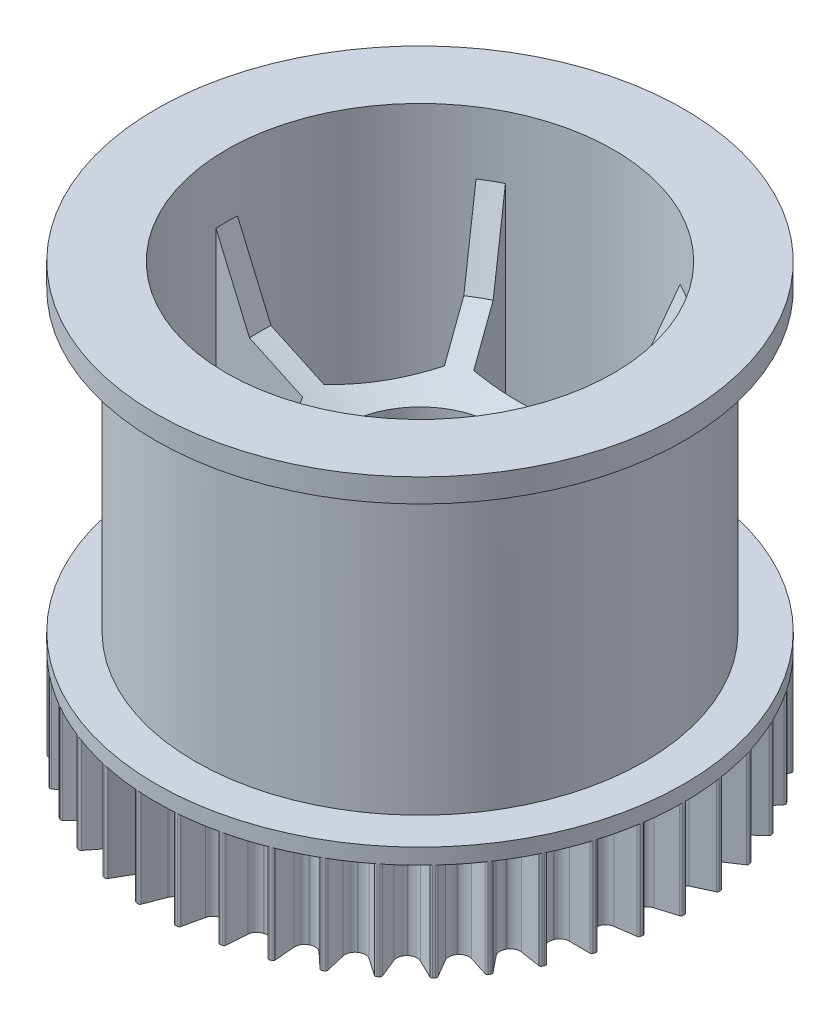
SolidWorks part; units mm, degrees
ref_plane "前视基准面" through (0, 0, 0) normal (0, 0, 1) x (1, 0, 0)
ref_plane "上视基准面" through (0, 0, 0) normal (0, 1, 0) x (1, 0, 0)
ref_plane "右视基准面" through (0, 0, 0) normal (1, 0, 0) x (0, 0, -1)
other "Configuration Table"
sketch "草图1" plane through (0, 0, 0) normal (0, 1, 0) x (1, 0, 0)
  line L0 (0, 0) -> (7.9279, 0) construction
  line L1 (0, 0) -> (0, 4.4256) construction
  line L2 (12.4216, 0.4494) -> (13.4287, 0.1463)
  line L3 (12.4216, -0.4494) -> (13.4287, -0.1463)
  line L4 (12.2159, -2.2957) -> (13.2569, -2.1461)
  line L5 (12.3499, -1.407) -> (13.3005, -1.8568)
  line L6 (11.7373, -4.0908) -> (12.789, -4.098)
  line L7 (12.0023, -3.2319) -> (12.8752, -3.8184)
  line L8 (10.9965, -5.7945) -> (12.0354, -5.9583)
  line L9 (11.3865, -4.9846) -> (12.1623, -5.6947)
  line L10 (10.0101, -7.3687) -> (11.0129, -7.6855)
  line L11 (10.5164, -6.626) -> (11.1777, -7.4438)
  line L12 (8.8, -8.7783) -> (9.7445, -9.2411)
  line L13 (9.4114, -8.1194) -> (9.9434, -9.0266)
  line L14 (7.3934, -9.9918) -> (8.2583, -10.5902)
  line L15 (8.0961, -9.4314) -> (8.487, -10.4078)
  line L16 (5.8216, -10.9822) -> (6.5877, -11.7028)
  line L17 (6.6, -10.5328) -> (6.841, -11.5565)
  line L18 (4.1198, -11.7272) -> (4.7699, -12.5539)
  line L19 (4.9565, -11.3988) -> (5.0422, -12.447)
  line L20 (2.3259, -12.2102) -> (2.8456, -13.1246)
  line L21 (3.2022, -12.0102) -> (3.1308, -13.0595)
  line L22 (0.4801, -12.4205) -> (0.8577, -13.4021)
  line L23 (1.3764, -12.3533) -> (1.1494, -13.3802)
  line L24 (-1.3764, -12.3533) -> (-1.1494, -13.3802)
  line L25 (-0.4801, -12.4205) -> (-0.8577, -13.4021)
  line L26 (-3.2022, -12.0102) -> (-3.1308, -13.0595)
  line L27 (-2.3259, -12.2102) -> (-2.8456, -13.1246)
  line L28 (-4.9565, -11.3988) -> (-5.0422, -12.447)
  line L29 (-4.1198, -11.7272) -> (-4.7699, -12.5539)
  line L30 (-6.6, -10.5328) -> (-6.841, -11.5565)
  line L31 (-5.8216, -10.9822) -> (-6.5877, -11.7028)
  line L32 (-8.0961, -9.4314) -> (-8.487, -10.4078)
  line L33 (-7.3934, -9.9918) -> (-8.2583, -10.5902)
  line L34 (-9.4114, -8.1194) -> (-9.9434, -9.0266)
  line L35 (-8.8, -8.7783) -> (-9.7445, -9.2411)
  line L36 (-10.5164, -6.626) -> (-11.1777, -7.4438)
  line L37 (-10.0101, -7.3687) -> (-11.0129, -7.6855)
  line L38 (-11.3865, -4.9846) -> (-12.1623, -5.6947)
  line L39 (-10.9965, -5.7945) -> (-12.0354, -5.9583)
  line L40 (-12.0023, -3.2319) -> (-12.8752, -3.8184)
  line L41 (-11.7373, -4.0908) -> (-12.789, -4.098)
  line L42 (-12.3499, -1.407) -> (-13.3005, -1.8568)
  line L43 (-12.2159, -2.2957) -> (-13.2569, -2.1461)
  line L44 (-12.4216, 0.4494) -> (-13.4287, 0.1463)
  line L45 (-12.4216, -0.4494) -> (-13.4287, -0.1463)
  line L46 (-12.2159, 2.2957) -> (-13.2569, 2.1461)
  line L47 (-12.3499, 1.407) -> (-13.3005, 1.8568)
  line L48 (-11.7373, 4.0908) -> (-12.789, 4.098)
  line L49 (-12.0023, 3.2319) -> (-12.8752, 3.8184)
  line L50 (-10.9965, 5.7945) -> (-12.0354, 5.9583)
  line L51 (-11.3865, 4.9846) -> (-12.1623, 5.6947)
  line L52 (-10.0101, 7.3687) -> (-11.0129, 7.6855)
  line L53 (-10.5164, 6.626) -> (-11.1777, 7.4438)
  line L54 (-8.8, 8.7783) -> (-9.7445, 9.2411)
  line L55 (-9.4114, 8.1194) -> (-9.9434, 9.0266)
  line L56 (-7.3934, 9.9918) -> (-8.2583, 10.5902)
  line L57 (-8.0961, 9.4314) -> (-8.487, 10.4078)
  line L58 (-5.8216, 10.9822) -> (-6.5877, 11.7028)
  line L59 (-6.6, 10.5328) -> (-6.841, 11.5565)
  line L60 (-4.1198, 11.7272) -> (-4.7699, 12.5539)
  line L61 (-4.9565, 11.3988) -> (-5.0422, 12.447)
  line L62 (-2.3259, 12.2102) -> (-2.8456, 13.1246)
  line L63 (-3.2022, 12.0102) -> (-3.1308, 13.0595)
  line L64 (-0.4801, 12.4205) -> (-0.8577, 13.4021)
  line L65 (-1.3764, 12.3533) -> (-1.1494, 13.3802)
  line L66 (1.3764, 12.3533) -> (1.1494, 13.3802)
  line L67 (0.4801, 12.4205) -> (0.8577, 13.4021)
  line L68 (3.2022, 12.0102) -> (3.1308, 13.0595)
  line L69 (2.3259, 12.2102) -> (2.8456, 13.1246)
  line L70 (4.9565, 11.3988) -> (5.0422, 12.447)
  line L71 (4.1198, 11.7272) -> (4.7699, 12.5539)
  line L72 (6.6, 10.5328) -> (6.841, 11.5565)
  line L73 (5.8216, 10.9822) -> (6.5877, 11.7028)
  line L74 (8.0961, 9.4314) -> (8.487, 10.4078)
  line L75 (7.3934, 9.9918) -> (8.2583, 10.5902)
  line L76 (9.4114, 8.1194) -> (9.9434, 9.0266)
  line L77 (8.8, 8.7783) -> (9.7445, 9.2411)
  line L78 (10.5164, 6.626) -> (11.1777, 7.4438)
  line L79 (10.0101, 7.3687) -> (11.0129, 7.6855)
  line L80 (11.3865, 4.9846) -> (12.1623, 5.6947)
  line L81 (10.9965, 5.7945) -> (12.0354, 5.9583)
  line L82 (12.0023, 3.2319) -> (12.8752, 3.8184)
  line L83 (11.7373, 4.0908) -> (12.789, 4.098)
  line L84 (12.3499, 1.407) -> (13.3005, 1.8568)
  line L85 (12.2159, 2.2957) -> (13.2569, 2.1461)
  line L95 (2.8868, 5) -> (-2.8868, 5) construction
  line L96 (2.8868, 5) -> (5.456, 0.55) construction
  line L97 (0, 0) -> (2.8868, 5) construction
  line L98 (-2.8868, 5) -> (-5.456, 0.55) construction
  line L99 (3.2043, -4.45) -> (5.456, -0.55)
  line L100 (2.2517, -5) -> (-2.2517, -5)
  line L101 (-3.2043, -4.45) -> (-5.456, -0.55)
  line L102 (8.1752, 0) -> (11.2, 0) construction
  line L103 (5.456, 0.55) -> (11.1865, 0.55)
  line L104 (5.456, -0.55) -> (11.1865, -0.55)
  line L105 (3.2043, -4.45) -> (6.0696, -9.4128)
  line L106 (2.2517, -5) -> (5.1169, -9.9628)
  line L107 (-2.2517, -5) -> (-5.1169, -9.9628)
  line L108 (-3.2043, -4.45) -> (-6.0696, -9.4128)
  line L109 (-5.456, -0.55) -> (-11.1865, -0.55)
  line L110 (-5.456, 0.55) -> (-11.1865, 0.55)
  line L111 (-3.2043, 4.45) -> (-6.0696, 9.4128)
  line L112 (-2.2517, 5) -> (-5.1169, 9.9628)
  line L113 (2.2517, 5) -> (5.1169, 9.9628)
  line L114 (3.2043, 4.45) -> (6.0696, 9.4128)
  line L115 (0, 0) -> (12.0337, 1.2648) construction
  line L116 (12.0337, -1.2648) -> (0, 0) construction
  line L117 (-5.456, 0.55) -> (-3.2043, 4.45)
  line L118 (-2.2517, 5) -> (2.2517, 5)
  line L119 (3.2043, 4.45) -> (5.456, 0.55)
  circle A0 centre (0, 0) radius 11.2 construction
  circle A1 centre (0, 0) radius 12.1 construction
  circle A2 centre (0, 0) radius 13.5 construction
  arc A3 (13.4999, 0.0509) -> (13.4999, -0.0509) centre (0, 0) cw
  arc A4 (12.0671, 0.8914) -> (12.0337, 1.2648) centre (0, 0) ccw construction
  arc A5 (13.4287, -0.1463) -> (13.4999, -0.0509) centre (13.3999, -0.0505) ccw
  arc A6 (13.4287, 0.1463) -> (13.4999, 0.0509) centre (13.3999, 0.0505) cw
  arc A7 (12.0671, -0.8914) -> (12.0337, -1.2648) centre (0, 0) cw construction
  arc A8 (12.4216, -0.4494) -> (12.0671, -0.8914) centre (12.5658, -0.9282) ccw
  arc A9 (12.4216, 0.4494) -> (12.0671, 0.8914) centre (12.5658, 0.9282) cw
  arc A10 (12.2159, -2.2957) -> (11.7995, -2.6799) centre (12.2871, -2.7907) ccw
  arc A11 (12.3499, -1.407) -> (12.0652, -0.9171) centre (12.5638, -0.955) cw
  arc A12 (13.3005, -1.8568) -> (13.3567, -1.9617) centre (13.2578, -1.9472) cw
  arc A13 (13.3567, -1.9617) -> (13.3415, -2.0624) centre (0, 0) cw
  arc A14 (13.2569, -2.1461) -> (13.3415, -2.0624) centre (13.2427, -2.0471) ccw
  arc A15 (11.7373, -4.0908) -> (11.2683, -4.4086) centre (11.7339, -4.5908) ccw
  arc A16 (12.0023, -3.2319) -> (11.7937, -2.7051) centre (12.2811, -2.8169) cw
  arc A17 (12.8752, -3.8184) -> (12.9151, -3.9305) centre (12.8195, -3.9014) cw
  arc A18 (12.9151, -3.9305) -> (12.8851, -4.0278) centre (0, 0) cw
  arc A19 (12.789, -4.098) -> (12.8851, -4.0278) centre (12.7897, -3.998) ccw
  arc A20 (10.9965, -5.7945) -> (10.4854, -6.0388) centre (10.9186, -6.2884) ccw
  arc A21 (11.3865, -4.9846) -> (11.2589, -4.4326) centre (11.7241, -4.6158) cw
  arc A22 (12.1623, -5.6947) -> (12.1851, -5.8115) centre (12.0948, -5.7685) cw
  arc A23 (12.1851, -5.8115) -> (12.1409, -5.9032) centre (0, 0) cw
  arc A24 (12.0354, -5.9583) -> (12.1409, -5.9032) centre (12.051, -5.8595) ccw
  arc A25 (10.0101, -7.3687) -> (9.4682, -7.5341) centre (9.8595, -7.8455) ccw
  arc A26 (10.5164, -6.626) -> (10.4724, -6.0612) centre (10.9052, -6.3116) cw
  arc A27 (11.1777, -7.4438) -> (11.1828, -7.5627) centre (11.1, -7.5067) cw
  arc A28 (11.1828, -7.5627) -> (11.1255, -7.6468) centre (0, 0) cw
  arc A29 (11.0129, -7.6855) -> (11.1255, -7.6468) centre (11.0431, -7.5902) ccw
  arc A30 (8.8, -8.7783) -> (8.2395, -8.8611) centre (8.58, -9.2273) ccw
  arc A31 (9.4114, -8.1194) -> (9.4521, -7.5543) centre (9.8427, -7.8665) cw
  arc A32 (9.9434, -9.0266) -> (9.9308, -9.145) centre (9.8572, -9.0772) cw
  arc A33 (9.9308, -9.145) -> (9.8615, -9.2196) centre (0, 0) cw
  arc A34 (9.7445, -9.2411) -> (9.8615, -9.2196) centre (9.7885, -9.1513) ccw
  arc A35 (7.3934, -9.9918) -> (6.8268, -9.9902) centre (7.1089, -10.403) ccw
  arc A36 (8.0961, -9.4314) -> (8.2206, -8.8787) centre (8.5603, -9.2456) cw
  arc A37 (8.487, -10.4078) -> (8.4568, -10.5229) centre (8.3942, -10.445) cw
  arc A38 (8.4568, -10.5229) -> (8.3773, -10.5864) centre (0, 0) cw
  arc A39 (8.2583, -10.5902) -> (8.3773, -10.5864) centre (8.3152, -10.508) ccw
  arc A40 (5.8216, -10.9822) -> (5.2616, -10.8961) centre (5.479, -11.3464) ccw
  arc A41 (6.6, -10.5328) -> (6.8055, -10.0048) centre (7.0867, -10.4182) cw
  arc A42 (6.841, -11.5565) -> (6.794, -11.6658) centre (6.7437, -11.5794) cw
  arc A43 (6.794, -11.6658) -> (6.7059, -11.7167) centre (0, 0) cw
  arc A44 (6.5877, -11.7028) -> (6.7059, -11.7167) centre (6.6562, -11.6299) ccw
  arc A45 (4.1198, -11.7272) -> (3.5789, -11.5586) centre (3.7268, -12.0362) ccw
  arc A46 (4.9565, -11.3988) -> (5.2384, -10.9073) centre (5.4548, -11.358) cw
  arc A47 (5.0422, -12.447) -> (4.9795, -12.5481) centre (4.9426, -12.4552) cw
  arc A48 (4.9795, -12.5481) -> (4.8847, -12.5853) centre (0, 0) cw
  arc A49 (4.7699, -12.5539) -> (4.8847, -12.5853) centre (4.8485, -12.4921) ccw
  arc A50 (2.3259, -12.2102) -> (1.8162, -11.9629) centre (1.8912, -12.4573) ccw
  arc A51 (3.2022, -12.0102) -> (3.5542, -11.5662) centre (3.7011, -12.0442) cw
  arc A52 (3.1308, -13.0595) -> (3.0536, -13.1501) centre (3.031, -13.0527) cw
  arc A53 (3.0536, -13.1501) -> (2.9544, -13.1728) centre (0, 0) cw
  arc A54 (2.8456, -13.1246) -> (2.9544, -13.1728) centre (2.9325, -13.0752) ccw
  arc A55 (0.4801, -12.4205) -> (0.0129, -12.1) centre (0.0134, -12.6) ccw
  arc A56 (1.3764, -12.3533) -> (1.7906, -11.9668) centre (1.8646, -12.4613) cw
  arc A57 (1.1494, -13.3802) -> (1.0596, -13.4584) centre (1.0518, -13.3587) cw
  arc A58 (1.0596, -13.4584) -> (0.9581, -13.466) centre (0, 0) cw
  arc A59 (0.8577, -13.4021) -> (0.9581, -13.466) centre (0.951, -13.3662) ccw
  arc A60 (-1.3764, -12.3533) -> (-1.7906, -11.9668) centre (-1.8646, -12.4613) ccw
  arc A61 (-0.4801, -12.4205) -> (-0.0129, -12.1) centre (-0.0134, -12.6) cw
  arc A62 (-0.8577, -13.4021) -> (-0.9581, -13.466) centre (-0.951, -13.3662) cw
  arc A63 (-0.9581, -13.466) -> (-1.0596, -13.4584) centre (0, 0) cw
  arc A64 (-1.1494, -13.3802) -> (-1.0596, -13.4584) centre (-1.0518, -13.3587) ccw
  arc A65 (-3.2022, -12.0102) -> (-3.5542, -11.5662) centre (-3.7011, -12.0442) ccw
  arc A66 (-2.3259, -12.2102) -> (-1.8162, -11.9629) centre (-1.8912, -12.4573) cw
  arc A67 (-2.8456, -13.1246) -> (-2.9544, -13.1728) centre (-2.9325, -13.0752) cw
  arc A68 (-2.9544, -13.1728) -> (-3.0536, -13.1501) centre (0, 0) cw
  arc A69 (-3.1308, -13.0595) -> (-3.0536, -13.1501) centre (-3.031, -13.0527) ccw
  arc A70 (-4.9565, -11.3988) -> (-5.2384, -10.9073) centre (-5.4548, -11.358) ccw
  arc A71 (-4.1198, -11.7272) -> (-3.5789, -11.5586) centre (-3.7268, -12.0362) cw
  arc A72 (-4.7699, -12.5539) -> (-4.8847, -12.5853) centre (-4.8485, -12.4921) cw
  arc A73 (-4.8847, -12.5853) -> (-4.9795, -12.5481) centre (0, 0) cw
  arc A74 (-5.0422, -12.447) -> (-4.9795, -12.5481) centre (-4.9426, -12.4552) ccw
  arc A75 (-6.6, -10.5328) -> (-6.8055, -10.0048) centre (-7.0867, -10.4182) ccw
  arc A76 (-5.8216, -10.9822) -> (-5.2616, -10.8961) centre (-5.479, -11.3464) cw
  arc A77 (-6.5877, -11.7028) -> (-6.7059, -11.7167) centre (-6.6562, -11.6299) cw
  arc A78 (-6.7059, -11.7167) -> (-6.794, -11.6658) centre (0, 0) cw
  arc A79 (-6.841, -11.5565) -> (-6.794, -11.6658) centre (-6.7437, -11.5794) ccw
  arc A80 (-8.0961, -9.4314) -> (-8.2206, -8.8787) centre (-8.5603, -9.2456) ccw
  arc A81 (-7.3934, -9.9918) -> (-6.8268, -9.9902) centre (-7.1089, -10.403) cw
  arc A82 (-8.2583, -10.5902) -> (-8.3773, -10.5864) centre (-8.3152, -10.508) cw
  arc A83 (-8.3773, -10.5864) -> (-8.4568, -10.5229) centre (0, 0) cw
  arc A84 (-8.487, -10.4078) -> (-8.4568, -10.5229) centre (-8.3942, -10.445) ccw
  arc A85 (-9.4114, -8.1194) -> (-9.4521, -7.5543) centre (-9.8427, -7.8665) ccw
  arc A86 (-8.8, -8.7783) -> (-8.2395, -8.8611) centre (-8.58, -9.2273) cw
  arc A87 (-9.7445, -9.2411) -> (-9.8615, -9.2196) centre (-9.7885, -9.1513) cw
  arc A88 (-9.8615, -9.2196) -> (-9.9308, -9.145) centre (0, 0) cw
  arc A89 (-9.9434, -9.0266) -> (-9.9308, -9.145) centre (-9.8572, -9.0772) ccw
  arc A90 (-10.5164, -6.626) -> (-10.4724, -6.0612) centre (-10.9052, -6.3116) ccw
  arc A91 (-10.0101, -7.3687) -> (-9.4682, -7.5341) centre (-9.8595, -7.8455) cw
  arc A92 (-11.0129, -7.6855) -> (-11.1255, -7.6468) centre (-11.0431, -7.5902) cw
  arc A93 (-11.1255, -7.6468) -> (-11.1828, -7.5627) centre (0, 0) cw
  arc A94 (-11.1777, -7.4438) -> (-11.1828, -7.5627) centre (-11.1, -7.5067) ccw
  arc A95 (-11.3865, -4.9846) -> (-11.2589, -4.4326) centre (-11.7241, -4.6158) ccw
  arc A96 (-10.9965, -5.7945) -> (-10.4854, -6.0388) centre (-10.9186, -6.2884) cw
  arc A97 (-12.0354, -5.9583) -> (-12.1409, -5.9032) centre (-12.051, -5.8595) cw
  arc A98 (-12.1409, -5.9032) -> (-12.1851, -5.8115) centre (0, 0) cw
  arc A99 (-12.1623, -5.6947) -> (-12.1851, -5.8115) centre (-12.0948, -5.7685) ccw
  arc A100 (-12.0023, -3.2319) -> (-11.7937, -2.7051) centre (-12.2811, -2.8169) ccw
  arc A101 (-11.7373, -4.0908) -> (-11.2683, -4.4086) centre (-11.7339, -4.5908) cw
  arc A102 (-12.789, -4.098) -> (-12.8851, -4.0278) centre (-12.7897, -3.998) cw
  arc A103 (-12.8851, -4.0278) -> (-12.9151, -3.9305) centre (0, 0) cw
  arc A104 (-12.8752, -3.8184) -> (-12.9151, -3.9305) centre (-12.8195, -3.9014) ccw
  arc A105 (-12.3499, -1.407) -> (-12.0652, -0.9171) centre (-12.5638, -0.955) ccw
  arc A106 (-12.2159, -2.2957) -> (-11.7995, -2.6799) centre (-12.2871, -2.7907) cw
  arc A107 (-13.2569, -2.1461) -> (-13.3415, -2.0624) centre (-13.2427, -2.0471) cw
  arc A108 (-13.3415, -2.0624) -> (-13.3567, -1.9617) centre (0, 0) cw
  arc A109 (-13.3005, -1.8568) -> (-13.3567, -1.9617) centre (-13.2578, -1.9472) ccw
  arc A110 (-12.4216, 0.4494) -> (-12.0671, 0.8914) centre (-12.5658, 0.9282) ccw
  arc A111 (-12.4216, -0.4494) -> (-12.0671, -0.8914) centre (-12.5658, -0.9282) cw
  arc A112 (-13.4287, -0.1463) -> (-13.4999, -0.0509) centre (-13.3999, -0.0505) cw
  arc A113 (-13.4999, -0.0509) -> (-13.4999, 0.0509) centre (0, 0) cw
  arc A114 (-13.4287, 0.1463) -> (-13.4999, 0.0509) centre (-13.3999, 0.0505) ccw
  arc A115 (-12.2159, 2.2957) -> (-11.7995, 2.6799) centre (-12.2871, 2.7907) ccw
  arc A116 (-12.3499, 1.407) -> (-12.0652, 0.9171) centre (-12.5638, 0.955) cw
  arc A117 (-13.3005, 1.8568) -> (-13.3567, 1.9617) centre (-13.2578, 1.9472) cw
  arc A118 (-13.3567, 1.9617) -> (-13.3415, 2.0624) centre (0, 0) cw
  arc A119 (-13.2569, 2.1461) -> (-13.3415, 2.0624) centre (-13.2427, 2.0471) ccw
  arc A120 (-11.7373, 4.0908) -> (-11.2683, 4.4086) centre (-11.7339, 4.5908) ccw
  arc A121 (-12.0023, 3.2319) -> (-11.7937, 2.7051) centre (-12.2811, 2.8169) cw
  arc A122 (-12.8752, 3.8184) -> (-12.9151, 3.9305) centre (-12.8195, 3.9014) cw
  arc A123 (-12.9151, 3.9305) -> (-12.8851, 4.0278) centre (0, 0) cw
  arc A124 (-12.789, 4.098) -> (-12.8851, 4.0278) centre (-12.7897, 3.998) ccw
  arc A125 (-10.9965, 5.7945) -> (-10.4854, 6.0388) centre (-10.9186, 6.2884) ccw
  arc A126 (-11.3865, 4.9846) -> (-11.2589, 4.4326) centre (-11.7241, 4.6158) cw
  arc A127 (-12.1623, 5.6947) -> (-12.1851, 5.8115) centre (-12.0948, 5.7685) cw
  arc A128 (-12.1851, 5.8115) -> (-12.1409, 5.9032) centre (0, 0) cw
  arc A129 (-12.0354, 5.9583) -> (-12.1409, 5.9032) centre (-12.051, 5.8595) ccw
  arc A130 (-10.0101, 7.3687) -> (-9.4682, 7.5341) centre (-9.8595, 7.8455) ccw
  arc A131 (-10.5164, 6.626) -> (-10.4724, 6.0612) centre (-10.9052, 6.3116) cw
  arc A132 (-11.1777, 7.4438) -> (-11.1828, 7.5627) centre (-11.1, 7.5067) cw
  arc A133 (-11.1828, 7.5627) -> (-11.1255, 7.6468) centre (0, 0) cw
  arc A134 (-11.0129, 7.6855) -> (-11.1255, 7.6468) centre (-11.0431, 7.5902) ccw
  arc A135 (-8.8, 8.7783) -> (-8.2395, 8.8611) centre (-8.58, 9.2273) ccw
  arc A136 (-9.4114, 8.1194) -> (-9.4521, 7.5543) centre (-9.8427, 7.8665) cw
  arc A137 (-9.9434, 9.0266) -> (-9.9308, 9.145) centre (-9.8572, 9.0772) cw
  arc A138 (-9.9308, 9.145) -> (-9.8615, 9.2196) centre (0, 0) cw
  arc A139 (-9.7445, 9.2411) -> (-9.8615, 9.2196) centre (-9.7885, 9.1513) ccw
  arc A140 (-7.3934, 9.9918) -> (-6.8268, 9.9902) centre (-7.1089, 10.403) ccw
  arc A141 (-8.0961, 9.4314) -> (-8.2206, 8.8787) centre (-8.5603, 9.2456) cw
  arc A142 (-8.487, 10.4078) -> (-8.4568, 10.5229) centre (-8.3942, 10.445) cw
  arc A143 (-8.4568, 10.5229) -> (-8.3773, 10.5864) centre (0, 0) cw
  arc A144 (-8.2583, 10.5902) -> (-8.3773, 10.5864) centre (-8.3152, 10.508) ccw
  arc A145 (-5.8216, 10.9822) -> (-5.2616, 10.8961) centre (-5.479, 11.3464) ccw
  arc A146 (-6.6, 10.5328) -> (-6.8055, 10.0048) centre (-7.0867, 10.4182) cw
  arc A147 (-6.841, 11.5565) -> (-6.794, 11.6658) centre (-6.7437, 11.5794) cw
  arc A148 (-6.794, 11.6658) -> (-6.7059, 11.7167) centre (0, 0) cw
  arc A149 (-6.5877, 11.7028) -> (-6.7059, 11.7167) centre (-6.6562, 11.6299) ccw
  arc A150 (-4.1198, 11.7272) -> (-3.5789, 11.5586) centre (-3.7268, 12.0362) ccw
  arc A151 (-4.9565, 11.3988) -> (-5.2384, 10.9073) centre (-5.4548, 11.358) cw
  arc A152 (-5.0422, 12.447) -> (-4.9795, 12.5481) centre (-4.9426, 12.4552) cw
  arc A153 (-4.9795, 12.5481) -> (-4.8847, 12.5853) centre (0, 0) cw
  arc A154 (-4.7699, 12.5539) -> (-4.8847, 12.5853) centre (-4.8485, 12.4921) ccw
  arc A155 (-2.3259, 12.2102) -> (-1.8162, 11.9629) centre (-1.8912, 12.4573) ccw
  arc A156 (-3.2022, 12.0102) -> (-3.5542, 11.5662) centre (-3.7011, 12.0442) cw
  arc A157 (-3.1308, 13.0595) -> (-3.0536, 13.1501) centre (-3.031, 13.0527) cw
  arc A158 (-3.0536, 13.1501) -> (-2.9544, 13.1728) centre (0, 0) cw
  arc A159 (-2.8456, 13.1246) -> (-2.9544, 13.1728) centre (-2.9325, 13.0752) ccw
  arc A160 (-0.4801, 12.4205) -> (-0.0129, 12.1) centre (-0.0134, 12.6) ccw
  arc A161 (-1.3764, 12.3533) -> (-1.7906, 11.9668) centre (-1.8646, 12.4613) cw
  arc A162 (-1.1494, 13.3802) -> (-1.0596, 13.4584) centre (-1.0518, 13.3587) cw
  arc A163 (-1.0596, 13.4584) -> (-0.9581, 13.466) centre (0, 0) cw
  arc A164 (-0.8577, 13.4021) -> (-0.9581, 13.466) centre (-0.951, 13.3662) ccw
  arc A165 (1.3764, 12.3533) -> (1.7906, 11.9668) centre (1.8646, 12.4613) ccw
  arc A166 (0.4801, 12.4205) -> (0.0129, 12.1) centre (0.0134, 12.6) cw
  arc A167 (0.8577, 13.4021) -> (0.9581, 13.466) centre (0.951, 13.3662) cw
  arc A168 (0.9581, 13.466) -> (1.0596, 13.4584) centre (0, 0) cw
  arc A169 (1.1494, 13.3802) -> (1.0596, 13.4584) centre (1.0518, 13.3587) ccw
  arc A170 (3.2022, 12.0102) -> (3.5542, 11.5662) centre (3.7011, 12.0442) ccw
  arc A171 (2.3259, 12.2102) -> (1.8162, 11.9629) centre (1.8912, 12.4573) cw
  arc A172 (2.8456, 13.1246) -> (2.9544, 13.1728) centre (2.9325, 13.0752) cw
  arc A173 (2.9544, 13.1728) -> (3.0536, 13.1501) centre (0, 0) cw
  arc A174 (3.1308, 13.0595) -> (3.0536, 13.1501) centre (3.031, 13.0527) ccw
  arc A175 (4.9565, 11.3988) -> (5.2384, 10.9073) centre (5.4548, 11.358) ccw
  arc A176 (4.1198, 11.7272) -> (3.5789, 11.5586) centre (3.7268, 12.0362) cw
  arc A177 (4.7699, 12.5539) -> (4.8847, 12.5853) centre (4.8485, 12.4921) cw
  arc A178 (4.8847, 12.5853) -> (4.9795, 12.5481) centre (0, 0) cw
  arc A179 (5.0422, 12.447) -> (4.9795, 12.5481) centre (4.9426, 12.4552) ccw
  arc A180 (6.6, 10.5328) -> (6.8055, 10.0048) centre (7.0867, 10.4182) ccw
  arc A181 (5.8216, 10.9822) -> (5.2616, 10.8961) centre (5.479, 11.3464) cw
  arc A182 (6.5877, 11.7028) -> (6.7059, 11.7167) centre (6.6562, 11.6299) cw
  arc A183 (6.7059, 11.7167) -> (6.794, 11.6658) centre (0, 0) cw
  arc A184 (6.841, 11.5565) -> (6.794, 11.6658) centre (6.7437, 11.5794) ccw
  arc A185 (8.0961, 9.4314) -> (8.2206, 8.8787) centre (8.5603, 9.2456) ccw
  arc A186 (7.3934, 9.9918) -> (6.8268, 9.9902) centre (7.1089, 10.403) cw
  arc A187 (8.2583, 10.5902) -> (8.3773, 10.5864) centre (8.3152, 10.508) cw
  arc A188 (8.3773, 10.5864) -> (8.4568, 10.5229) centre (0, 0) cw
  arc A189 (8.487, 10.4078) -> (8.4568, 10.5229) centre (8.3942, 10.445) ccw
  arc A190 (9.4114, 8.1194) -> (9.4521, 7.5543) centre (9.8427, 7.8665) ccw
  arc A191 (8.8, 8.7783) -> (8.2395, 8.8611) centre (8.58, 9.2273) cw
  arc A192 (9.7445, 9.2411) -> (9.8615, 9.2196) centre (9.7885, 9.1513) cw
  arc A193 (9.8615, 9.2196) -> (9.9308, 9.145) centre (0, 0) cw
  arc A194 (9.9434, 9.0266) -> (9.9308, 9.145) centre (9.8572, 9.0772) ccw
  arc A195 (10.5164, 6.626) -> (10.4724, 6.0612) centre (10.9052, 6.3116) ccw
  arc A196 (10.0101, 7.3687) -> (9.4682, 7.5341) centre (9.8595, 7.8455) cw
  arc A197 (11.0129, 7.6855) -> (11.1255, 7.6468) centre (11.0431, 7.5902) cw
  arc A198 (11.1255, 7.6468) -> (11.1828, 7.5627) centre (0, 0) cw
  arc A199 (11.1777, 7.4438) -> (11.1828, 7.5627) centre (11.1, 7.5067) ccw
  arc A200 (11.3865, 4.9846) -> (11.2589, 4.4326) centre (11.7241, 4.6158) ccw
  arc A201 (10.9965, 5.7945) -> (10.4854, 6.0388) centre (10.9186, 6.2884) cw
  arc A202 (12.0354, 5.9583) -> (12.1409, 5.9032) centre (12.051, 5.8595) cw
  arc A203 (12.1409, 5.9032) -> (12.1851, 5.8115) centre (0, 0) cw
  arc A204 (12.1623, 5.6947) -> (12.1851, 5.8115) centre (12.0948, 5.7685) ccw
  arc A205 (12.0023, 3.2319) -> (11.7937, 2.7051) centre (12.2811, 2.8169) ccw
  arc A206 (11.7373, 4.0908) -> (11.2683, 4.4086) centre (11.7339, 4.5908) cw
  arc A207 (12.789, 4.098) -> (12.8851, 4.0278) centre (12.7897, 3.998) cw
  arc A208 (12.8851, 4.0278) -> (12.9151, 3.9305) centre (0, 0) cw
  arc A209 (12.8752, 3.8184) -> (12.9151, 3.9305) centre (12.8195, 3.9014) ccw
  arc A210 (12.3499, 1.407) -> (12.0652, 0.9171) centre (12.5638, 0.955) ccw
  arc A211 (12.2159, 2.2957) -> (11.7995, 2.6799) centre (12.2871, 2.7907) cw
  arc A212 (13.2569, 2.1461) -> (13.3415, 2.0624) centre (13.2427, 2.0471) cw
  arc A213 (13.3415, 2.0624) -> (13.3567, 1.9617) centre (0, 0) cw
  arc A214 (13.3005, 1.8568) -> (13.3567, 1.9617) centre (13.2578, 1.9472) ccw
  circle A216 centre (0, 0) radius 3.9
  arc A217 (11.1865, 0.55) -> (6.0696, 9.4128) centre (0, 0) ccw
  arc A218 (5.1169, 9.9628) -> (-5.1169, 9.9628) centre (0, 0) ccw
  arc A219 (-6.0696, 9.4128) -> (-11.1865, 0.55) centre (0, 0) ccw
  arc A220 (-11.1865, -0.55) -> (-6.0696, -9.4128) centre (0, 0) ccw
  arc A221 (-5.1169, -9.9628) -> (5.1169, -9.9628) centre (0, 0) ccw
  arc A222 (6.0696, -9.4128) -> (11.1865, -0.55) centre (0, 0) ccw
  arc A223 (12.0652, 0.9171) -> (12.0671, 0.8914) centre (0, 0) cw
  arc A224 (12.0671, -0.8914) -> (12.0652, -0.9171) centre (0, 0) cw
  arc A225 (11.7995, -2.6799) -> (11.7937, -2.7051) centre (0, 0) cw
  arc A226 (11.2683, -4.4086) -> (11.2589, -4.4326) centre (0, 0) cw
  arc A227 (10.4854, -6.0388) -> (10.4724, -6.0612) centre (0, 0) cw
  arc A228 (9.4682, -7.5341) -> (9.4521, -7.5543) centre (0, 0) cw
  arc A229 (8.2395, -8.8611) -> (8.2206, -8.8787) centre (0, 0) cw
  arc A230 (6.8268, -9.9902) -> (6.8055, -10.0048) centre (0, 0) cw
  arc A231 (5.2616, -10.8961) -> (5.2384, -10.9073) centre (0, 0) cw
  arc A232 (3.5789, -11.5586) -> (3.5542, -11.5662) centre (0, 0) cw
  arc A233 (1.8162, -11.9629) -> (1.7906, -11.9668) centre (0, 0) cw
  arc A234 (0.0129, -12.1) -> (-0.0129, -12.1) centre (0, 0) cw
  arc A235 (-1.7906, -11.9668) -> (-1.8162, -11.9629) centre (0, 0) cw
  arc A236 (-3.5542, -11.5662) -> (-3.5789, -11.5586) centre (0, 0) cw
  arc A237 (-5.2384, -10.9073) -> (-5.2616, -10.8961) centre (0, 0) cw
  arc A238 (-6.8055, -10.0048) -> (-6.8268, -9.9902) centre (0, 0) cw
  arc A239 (-8.2206, -8.8787) -> (-8.2395, -8.8611) centre (0, 0) cw
  arc A240 (-9.4521, -7.5543) -> (-9.4682, -7.5341) centre (0, 0) cw
  arc A241 (-10.4724, -6.0612) -> (-10.4854, -6.0388) centre (0, 0) cw
  arc A242 (-11.2589, -4.4326) -> (-11.2683, -4.4086) centre (0, 0) cw
  arc A243 (-11.7937, -2.7051) -> (-11.7995, -2.6799) centre (0, 0) cw
  arc A244 (-12.0652, -0.9171) -> (-12.0671, -0.8914) centre (0, 0) cw
  arc A245 (-12.0671, 0.8914) -> (-12.0652, 0.9171) centre (0, 0) cw
  arc A246 (-11.7995, 2.6799) -> (-11.7937, 2.7051) centre (0, 0) cw
  arc A247 (-11.2683, 4.4086) -> (-11.2589, 4.4326) centre (0, 0) cw
  arc A248 (-10.4854, 6.0388) -> (-10.4724, 6.0612) centre (0, 0) cw
  arc A249 (-9.4682, 7.5341) -> (-9.4521, 7.5543) centre (0, 0) cw
  arc A250 (-8.2395, 8.8611) -> (-8.2206, 8.8787) centre (0, 0) cw
  arc A251 (-6.8268, 9.9902) -> (-6.8055, 10.0048) centre (0, 0) cw
  arc A252 (-5.2616, 10.8961) -> (-5.2384, 10.9073) centre (0, 0) cw
  arc A253 (-3.5789, 11.5586) -> (-3.5542, 11.5662) centre (0, 0) cw
  arc A254 (-1.8162, 11.9629) -> (-1.7906, 11.9668) centre (0, 0) cw
  arc A255 (-0.0129, 12.1) -> (0.0129, 12.1) centre (0, 0) cw
  arc A256 (1.7906, 11.9668) -> (1.8162, 11.9629) centre (0, 0) cw
  arc A257 (3.5542, 11.5662) -> (3.5789, 11.5586) centre (0, 0) cw
  arc A258 (5.2384, 10.9073) -> (5.2616, 10.8961) centre (0, 0) cw
  arc A259 (6.8055, 10.0048) -> (6.8268, 9.9902) centre (0, 0) cw
  arc A260 (8.2206, 8.8787) -> (8.2395, 8.8611) centre (0, 0) cw
  arc A261 (9.4521, 7.5543) -> (9.4682, 7.5341) centre (0, 0) cw
  arc A262 (10.4724, 6.0612) -> (10.4854, 6.0388) centre (0, 0) cw
  arc A263 (11.2589, 4.4326) -> (11.2683, 4.4086) centre (0, 0) cw
  arc A264 (11.7937, 2.7051) -> (11.7995, 2.6799) centre (0, 0) cw
  point P17 (13.4994, -0.125)
  point P20 (13.4994, 0.125)
  point P23 (12.0875, -0.55)
  point P26 (12.0875, 0.55)
  point P524 (0, 5)
  dimension "D1" = 22.4
  dimension "D2" = 24.2
  dimension "D3" = 27
  dimension "D6" = 0.1
  dimension "D7" = 0.5
  dimension "D9" = 120
  dimension "D12" = 7.8
  dimension "D4" = 1.1
  dimension "D5" = 0.25
  dimension "D10" = 5
  dimension "D11" = 30
  dimension "D14" = 1.1
  dimension "D16" = 6
  dimension "D17" = 6
  dimension "D8" = 42
  dimension "D13" = 6
  dimension "D15" = 42
extrude "凸台-拉伸1" add sketch "草图1" along normal blind 5
sketch "草图2" plane through (0, 5, 0) normal (0, 1, 0) x (1, 0, 0)
  circle A0 centre (0, 0) radius 13.5
  arc A1 (13.3415, -2.0624) -> (13.3567, -1.9617) centre (0, 0) ccw construction
  circle A2 centre (0, 0) radius 11.2
  arc A3 (6.0696, -9.4128) -> (11.1865, -0.55) centre (0, 0) ccw construction
extrude "凸台-拉伸2" add sketch "草图2" along normal blind 0.8
extrude "拉伸-薄壁2" add sketch "草图2<2>" along normal blind 16 thin contours A2 thin type mid plane wall 0.6
sketch "草图2<2>" plane through (0, 5, 0) normal (0, 1, 0) x (1, 0, 0) same geometry as "草图2"
sketch "草图5" plane through (0, 21, 0) normal (0, 1, 0) x (1, 0, 0)
  circle A0 centre (0, 0) radius 13.5
  circle A1 centre (0, 0) radius 13.5 construction
  circle A2 centre (0, 0) radius 10.9
  circle A3 centre (0, 0) radius 10.9 construction
extrude "凸台-拉伸3" add sketch "草图5" along normal blind 1.2
sketch "草图6" plane through (0, 5, 0) normal (0, 1, 0) x (1, 0, 0)
  line L18 (-4.9667, -9.7027) -> (-2.2517, -5)
  line L19 (-2.2517, -5) -> (2.2517, -5)
  line L20 (2.2517, -5) -> (4.9667, -9.7027)
  line L21 (5.9194, -9.1527) -> (3.2043, -4.45)
  line L22 (3.2043, -4.45) -> (5.456, -0.55)
  line L23 (5.456, -0.55) -> (10.8861, -0.55)
  line L24 (10.8861, 0.55) -> (5.456, 0.55)
  line L25 (5.456, 0.55) -> (3.2043, 4.45)
  line L26 (3.2043, 4.45) -> (5.9194, 9.1527)
  line L27 (4.9667, 9.7027) -> (2.2517, 5)
  line L28 (2.2517, 5) -> (-2.2517, 5)
  line L29 (-2.2517, 5) -> (-4.9667, 9.7027)
  line L30 (-5.9194, 9.1527) -> (-3.2043, 4.45)
  line L31 (-3.2043, 4.45) -> (-5.456, 0.55)
  line L32 (-5.456, 0.55) -> (-10.8861, 0.55)
  line L33 (-10.8861, -0.55) -> (-5.456, -0.55)
  line L34 (-5.456, -0.55) -> (-3.2043, -4.45)
  line L35 (-3.2043, -4.45) -> (-5.9194, -9.1527)
  line L36 (-4.9667, -9.7027) -> (-2.2517, -5)
  line L37 (-2.2517, -5) -> (2.2517, -5)
  line L38 (2.2517, -5) -> (4.9667, -9.7027)
  line L39 (5.9194, -9.1527) -> (3.2043, -4.45)
  line L40 (3.2043, -4.45) -> (5.456, -0.55)
  line L41 (5.456, -0.55) -> (10.8861, -0.55)
  line L42 (10.8861, 0.55) -> (5.456, 0.55)
  line L43 (5.456, 0.55) -> (3.2043, 4.45)
  line L44 (3.2043, 4.45) -> (5.9194, 9.1527)
  line L45 (4.9667, 9.7027) -> (2.2517, 5)
  line L46 (2.2517, 5) -> (-2.2517, 5)
  line L47 (-2.2517, 5) -> (-4.9667, 9.7027)
  line L48 (-5.9194, 9.1527) -> (-3.2043, 4.45)
  line L49 (-3.2043, 4.45) -> (-5.456, 0.55)
  line L50 (-5.456, 0.55) -> (-10.8861, 0.55)
  line L51 (-10.8861, -0.55) -> (-5.456, -0.55)
  line L52 (-5.456, -0.55) -> (-3.2043, -4.45)
  line L53 (-3.2043, -4.45) -> (-5.9194, -9.1527)
  circle A0 centre (0, 0) radius 3.9
  circle A1 centre (0, 0) radius 3.9 construction
  arc A6 (-5.9194, -9.1527) -> (-4.9667, -9.7027) centre (0, 0) ccw
  arc A7 (4.9667, -9.7027) -> (5.9194, -9.1527) centre (0, 0) ccw
  arc A8 (10.8861, -0.55) -> (10.8861, 0.55) centre (0, 0) ccw
  arc A9 (5.9194, 9.1527) -> (4.9667, 9.7027) centre (0, 0) ccw
  arc A10 (-4.9667, 9.7027) -> (-5.9194, 9.1527) centre (0, 0) ccw
  arc A11 (-10.8861, 0.55) -> (-10.8861, -0.55) centre (0, 0) ccw
  arc A12 (-5.9194, -9.1527) -> (-4.9667, -9.7027) centre (0, 0) ccw
  arc A13 (4.9667, -9.7027) -> (5.9194, -9.1527) centre (0, 0) ccw
  arc A14 (10.8861, -0.55) -> (10.8861, 0.55) centre (0, 0) ccw
  arc A15 (5.9194, 9.1527) -> (4.9667, 9.7027) centre (0, 0) ccw
  arc A16 (-4.9667, 9.7027) -> (-5.9194, 9.1527) centre (0, 0) ccw
  arc A17 (-10.8861, 0.55) -> (-10.8861, -0.55) centre (0, 0) ccw
  dimension "D1" = 0
extrude "凸台-拉伸5" add sketch "草图6" along normal blind 8
sketch "草图8" plane through (0, 0, 0) normal (0, -1, 0) x (1, 0, 0)
  circle A0 centre (0, 0) radius 3.4
  circle A1 centre (0, 0) radius 3.9
  dimension "D1" = 7.8
  dimension "D2" = 6.8
extrude "凸台-拉伸6" add sketch "草图8" against normal up to surface (13 mm away) up to face at (0, 13, 0)
extrude "切除-拉伸1" cut sketch "草图8<2>" against normal blind 3
sketch "草图8<2>" plane through (0, 0, 0) normal (0, -1, 0) x (1, 0, 0) same geometry as "草图8"
sketch "草图9" plane through (0, 13, 0) normal (0, 1, 0) x (1, 0, 0)
  circle A0 centre (0, 0) radius 3.9
  dimension "D1" = 7.8
extrude "切除-拉伸2" cut sketch "草图9" against normal blind 3
sketch "草图10" plane through (0, 22.2, 0) normal (0, 1, 0) x (1, 0, 0)
  circle A0 centre (0, 0) radius 9.9
  circle A1 centre (0, 0) radius 11.5
  circle A3 centre (0, 0) radius 11.5 construction
  dimension "D1" = 23
  dimension "D2" = 19.8
extrude "凸台-拉伸8" add sketch "草图10" against normal up to surface (22.2 mm away) up to face at (0, 0, -3.9)
sketch "草图12" plane through (0, 0, 0) normal (0, 0, 1) x (1, 0, 0)
  line L0 (-3.9, 13) -> (-9.9, 13)
  line L1 (-9.9, 13) -> (-9.9, 19)
  line L2 (-9.9, 22.2) -> (-9.9, 13) construction
  line L3 (-9.9, 19) -> (-8.189, 15)
  line L4 (-8.189, 15) -> (-3.9, 13)
  line L5 (-8.189, 15) -> (-8.189, 13) construction
  line L6 (0, 0) -> (0, 20.3521) construction
  dimension "D1" = 6
  dimension "D2" = 2
  dimension "D3" = 25
revolve "旋转4" add sketch "草图12" angle 360 about L6
sketch "草图13" plane through (0, 0, 0) normal (0, -1, 0) x (1, 0, 0)
  line L0 (-5.4187, -8.2854) -> (-3.2043, -4.45) construction
  line L1 (-3.2043, -4.45) -> (-5.456, -0.55) construction
  line L2 (-5.456, -0.55) -> (-9.8847, -0.55) construction
  line L3 (2.2517, -5) -> (-2.2517, -5) construction
  line L4 (-2.2517, -5) -> (-4.466, -8.8354) construction
  line L5 (4.466, -8.8354) -> (2.2517, -5) construction
  line L6 (9.8847, -0.55) -> (5.456, -0.55) construction
  line L7 (5.456, -0.55) -> (3.2043, -4.45) construction
  line L8 (3.2043, -4.45) -> (5.4187, -8.2854) construction
  line L9 (3.2043, 4.45) -> (5.456, 0.55) construction
  line L10 (5.456, 0.55) -> (9.8847, 0.55) construction
  line L11 (5.4187, 8.2854) -> (3.2043, 4.45) construction
  line L12 (-2.2517, 5) -> (2.2517, 5) construction
  line L13 (2.2517, 5) -> (4.466, 8.8354) construction
  line L14 (-4.466, 8.8354) -> (-2.2517, 5) construction
  line L15 (-5.456, 0.55) -> (-3.2043, 4.45) construction
  line L16 (-3.2043, 4.45) -> (-5.4187, 8.2854) construction
  line L17 (-9.8847, 0.55) -> (-5.456, 0.55) construction
  line L18 (-5.4187, -8.2854) -> (-3.2043, -4.45)
  line L19 (-3.2043, -4.45) -> (-5.456, -0.55)
  line L20 (-5.456, -0.55) -> (-9.8847, -0.55)
  line L21 (2.2517, -5) -> (-2.2517, -5)
  line L22 (-2.2517, -5) -> (-4.466, -8.8354)
  line L23 (4.466, -8.8354) -> (2.2517, -5)
  line L24 (9.8847, -0.55) -> (5.456, -0.55)
  line L25 (5.456, -0.55) -> (3.2043, -4.45)
  line L26 (3.2043, -4.45) -> (5.4187, -8.2854)
  line L27 (3.2043, 4.45) -> (5.456, 0.55)
  line L28 (5.456, 0.55) -> (9.8847, 0.55)
  line L29 (5.4187, 8.2854) -> (3.2043, 4.45)
  line L30 (-2.2517, 5) -> (2.2517, 5)
  line L31 (2.2517, 5) -> (4.466, 8.8354)
  line L32 (-4.466, 8.8354) -> (-2.2517, 5)
  line L33 (-5.456, 0.55) -> (-3.2043, 4.45)
  line L34 (-3.2043, 4.45) -> (-5.4187, 8.2854)
  line L35 (-9.8847, 0.55) -> (-5.456, 0.55)
  arc A0 (-9.8847, -0.55) -> (-5.4187, -8.2854) centre (0, 0) ccw construction
  arc A1 (-4.466, -8.8354) -> (4.466, -8.8354) centre (0, 0) ccw construction
  arc A2 (5.4187, -8.2854) -> (9.8847, -0.55) centre (0, 0) ccw construction
  arc A3 (9.8847, 0.55) -> (5.4187, 8.2854) centre (0, 0) ccw construction
  arc A4 (4.466, 8.8354) -> (-4.466, 8.8354) centre (0, 0) ccw construction
  arc A5 (-5.4187, 8.2854) -> (-9.8847, 0.55) centre (0, 0) ccw construction
  arc A6 (-5.4187, 8.2854) -> (-9.8847, 0.55) centre (0, 0) ccw construction
  arc A7 (-9.8847, -0.55) -> (-5.4187, -8.2854) centre (0, 0) ccw
  arc A8 (-4.466, -8.8354) -> (4.466, -8.8354) centre (0, 0) ccw
  arc A9 (5.4187, -8.2854) -> (9.8847, -0.55) centre (0, 0) ccw
  arc A10 (9.8847, 0.55) -> (5.4187, 8.2854) centre (0, 0) ccw
  arc A11 (4.466, 8.8354) -> (-4.466, 8.8354) centre (0, 0) ccw
  arc A12 (-5.4187, 8.2854) -> (-9.8847, 0.55) centre (0, 0) ccw
  arc A13 (-5.4187, 8.2854) -> (-9.8847, 0.55) centre (0, 0) ccw
extrude "切除-拉伸3" cut sketch "草图13" against normal up to surface (22.2 mm away) contours L34 A12 L35 L33 | L31 A11 L32 L30 | L28 A10 L29 L27 | L26 A9 L24 L25 | L22 A8 L23 L21 | L20 A7 L18 L19 region at (-6.5418, 0, -3.7769) region at (0, 0, -7.5538) region at (6.5418, 0, -3.7769) region at (6.5418, 0, 3.7769) region at (0, 0, 7.5538) region at (-6.5418, 0, 3.7769) up to face at (0, 22.2, 13.5)
